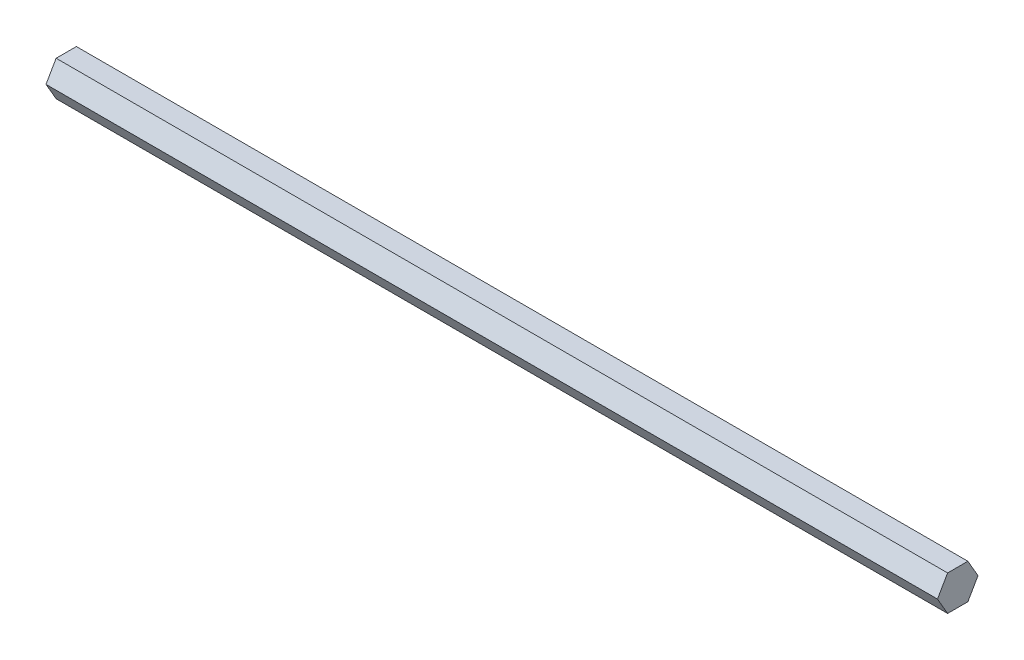
SolidWorks part; units mm, degrees
ref_plane "Front" through (0, 0, 0) normal (0, 0, 1) x (1, 0, 0)
ref_plane "Top" through (0, 0, 0) normal (0, 1, 0) x (1, 0, 0)
ref_plane "Right" through (0, 0, 0) normal (1, 0, 0) x (0, 0, -1)
sketch "Sketch1" plane through (0, 0, 0) normal (1, 0, 0) x (0, 0, -1)
  line L1 (1.4434, 2.5) -> (-1.4434, 2.5)
  line L2 (-1.4434, 2.5) -> (-2.8868, 0)
  line L3 (-2.8868, 0) -> (-1.4434, -2.5)
  line L4 (-1.4434, -2.5) -> (1.4434, -2.5)
  line L5 (1.4434, -2.5) -> (2.8868, 0)
  line L6 (2.8868, 0) -> (1.4434, 2.5)
  circle A0 centre (0, 0) radius 2.5 construction
  dimension "D1" = 5
extrude "Boss-Extrude1" add sketch "Sketch1" along normal blind 127
